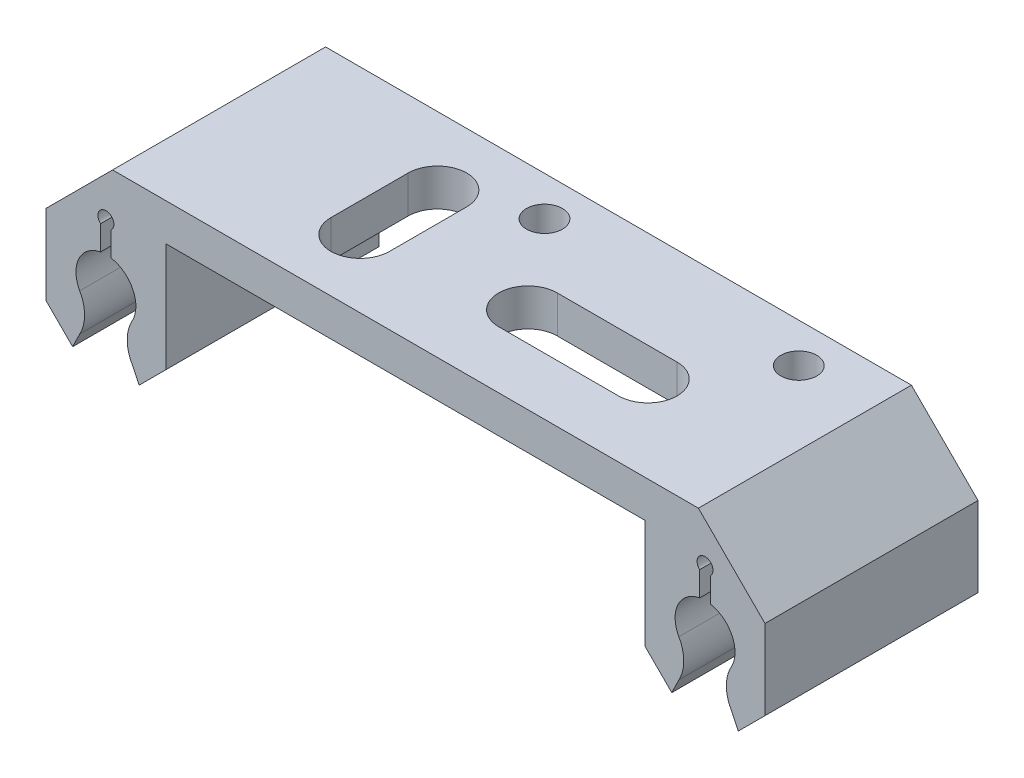
SolidWorks part; units mm, degrees
ref_plane "Front Plane" through (0, 0, 0) normal (0, 0, 1) x (1, 0, 0)
ref_plane "Top Plane" through (0, 0, 0) normal (0, 1, 0) x (1, 0, 0)
ref_plane "Right Plane" through (0, 0, 0) normal (1, 0, 0) x (0, 0, -1)
sketch "Sketch1" plane through (0, 0, 0) normal (0, 0, 1) x (1, 0, 0)
  line L0 (0, 0) -> (0, 13)
  line L1 (0, 13) -> (54, 13)
  line L2 (54, 13) -> (54, 0)
  line L3 (54, 0) -> (45, 0)
  line L4 (45, 0) -> (45, 10.2)
  line L5 (45, 10.2) -> (9, 10.2)
  line L6 (9, 10.2) -> (9, 0)
  line L7 (9, 0) -> (0, 0)
  point P4 (4.5, 0)
  dimension "D1" = 9
  dimension "D2" = 9
  dimension "D3" = 54
  dimension "D4" = 2.8
  dimension "D5" = 10.2
extrude "Boss-Extrude1" add sketch "Sketch1" along normal blind 16
chamfer "Chamfer1" distance 2 angle 45 4 edges at (54, 0, 8) (45, 0, 8) (0, 0, 8) (9, 0, 8)
sketch "Sketch2" plane through (0, 0, 16) normal (0, 0, 1) x (1, 0, 0)
  line L0 (2, 0) -> (7, 0) construction
  line L1 (47, 0) -> (52, 0) construction
  line L2 (9, 2) -> (9, 10.2) construction
  line L3 (45, 10.2) -> (45, 2) construction
  circle A0 centre (4.5, 5) radius 2.25
  circle A1 centre (49.5, 5) radius 2.25
  dimension "D5" = 4.5
  dimension "D6" = 4.5
  dimension "D1" = 5
  dimension "D2" = 5
  dimension "D3" = 4.5
  dimension "D4" = 4.5
extrude "Cut-Extrude1" cut sketch "Sketch2" against normal blind 16
sketch "Sketch3" plane through (0, 0, 16) normal (0, 0, 1) x (1, 0, 0)
  line L0 (2, 0) -> (7, 0) construction
  line L1 (4.1, 5) -> (4.1, 9.5) construction
  line L2 (4.1, 5) -> (4.9, 5) construction
  line L3 (4.1, 9.5) -> (4.9, 9.5) construction
  line L4 (4.9, 5) -> (4.9, 9.5) construction
  line L5 (4.1, 5) -> (4.9, 9.5) construction
  line L6 (4.1, 9.5) -> (4.9, 5) construction
  line L7 (2.5349, 3.9041) -> (6.4651, 3.9041)
  line L8 (2.5349, 1.0959) -> (2, 0)
  line L9 (2, 0) -> (7, 0)
  line L10 (7, 0) -> (6.4651, 1.0959)
  line L11 (2.9, 0) -> (2.9, 3.9041) construction
  line L12 (6.1, 3.9041) -> (6.1, 0) construction
  line L13 (4.1, 9.0528) -> (4.1, 6.7946)
  line L14 (4.1, 6.7946) -> (4.9, 6.7946)
  line L15 (4.9, 6.7946) -> (4.9, 9.0528)
  arc A0 (2.25, 0) -> (6.75, 0) centre (4.5, 0) cw construction
  circle A1 centre (4.5, 5) radius 2.25 construction
  arc A2 (2.5349, 3.9041) -> (2.5349, 1.0959) centre (0.0173, 2.5) cw
  arc A3 (6.4651, 3.9041) -> (6.4651, 1.0959) centre (8.9827, 2.5) ccw
  circle A4 centre (4.5, 9.5) radius 0.6 construction
  arc A5 (4.1, 9.0528) -> (4.9, 9.0528) centre (4.5, 9.5) cw
  point P6 (4.5, 7.25)
  dimension "D1" = 2.25
  dimension "D5" = 3.2
  dimension "D6" = 1.2
  dimension "D2" = 0.8
  dimension "D3" = 0.4
  dimension "D4" = 4.5
extrude "Cut-Extrude2" cut sketch "Sketch3" against normal blind 16
ref_plane "Plane1" through (27, 0, 0) normal (1, 0, 0) x (0, 0, -1)
mirror "Mirror1" about plane through (27, 0, 0) normal (1, 0, 0) of "Cut-Extrude2"
sketch "Sketch4" plane through (0, 13, 0) normal (0, 1, 0) x (1, 0, 0)
  line L0 (54, 0) -> (0, 0) construction
  line L1 (7.2, -16) -> (46.8, -16)
  line L2 (7.2, -16) -> (7.2, 0)
  line L3 (7.2, 0) -> (46.8, 0)
  line L4 (46.8, -16) -> (46.8, 0)
  line L5 (7.2, -16) -> (46.8, 0) construction
  line L6 (7.2, 0) -> (46.8, -16) construction
  line L7 (29.7, -9.5) -> (38.7, -9.5) construction
  line L8 (29.7, -7.3) -> (38.7, -7.3)
  line L9 (29.7, -11.7) -> (38.7, -11.7)
  line L10 (18.5, -5.1) -> (18.5, -10.9) construction
  line L11 (20.7, -5.1) -> (20.7, -10.9)
  line L12 (16.3, -5.1) -> (16.3, -10.9)
  circle A0 centre (43.5, -2.96) radius 1.6
  circle A1 centre (24.4, -2.96) radius 1.6
  arc A2 (29.7, -7.3) -> (29.7, -11.7) centre (29.7, -9.5) ccw
  arc A3 (38.7, -11.7) -> (38.7, -7.3) centre (38.7, -9.5) ccw
  arc A4 (20.7, -5.1) -> (16.3, -5.1) centre (18.5, -5.1) ccw
  arc A5 (16.3, -10.9) -> (20.7, -10.9) centre (18.5, -10.9) ccw
  point P0 (27, -8)
  point P8 (27, 0)
  point P12 (34.2, -9.5)
  point P21 (18.5, -8)
  point P26 (0, 0)
  point P27 (7.2, -8)
  dimension "D4" = 3.2
  dimension "D5" = 3.2
  dimension "D1" = 8
  dimension "D2" = 39.6
  dimension "D3" = 16
  dimension "D6" = 3.3
  dimension "D7" = 2.96
  dimension "D8" = 22.4
  dimension "D9" = 4.4
  dimension "D10" = 6.5
  dimension "D11" = 9
  dimension "D12" = 12.6
  dimension "D13" = 4.4
  dimension "D14" = 11.3
  dimension "D15" = 5.8
sketch "Sketch5" plane through (0, 13, 0) normal (0, 1, 0) x (1, 0, 0)
  line L0 (18.5, -5.1) -> (18.5, -10.9) construction
  line L1 (20.7, -5.1) -> (20.7, -10.9)
  line L2 (16.3, -5.1) -> (16.3, -10.9)
  line L3 (29.7, -9.5) -> (38.7, -9.5) construction
  line L4 (29.7, -7.3) -> (38.7, -7.3)
  line L5 (29.7, -11.7) -> (38.7, -11.7)
  arc A0 (20.7, -5.1) -> (16.3, -5.1) centre (18.5, -5.1) ccw
  arc A1 (16.3, -10.9) -> (20.7, -10.9) centre (18.5, -10.9) ccw
  arc A2 (29.7, -7.3) -> (29.7, -11.7) centre (29.7, -9.5) ccw
  arc A3 (38.7, -11.7) -> (38.7, -7.3) centre (38.7, -9.5) ccw
  circle A4 centre (24.4, -2.96) radius 1.35
  circle A5 centre (43.5, -2.96) radius 1.35
  point P4 (18.5, -8)
  point P9 (34.2, -9.5)
  point P24 (34.2, -11.7)
  dimension "D3" = 2.7
  dimension "D4" = 2.7
  dimension "D1" = 4.4
  dimension "D2" = 4.4
extrude "Cut-Extrude3" cut sketch "Sketch5" against normal blind 16
chamfer "Chamfer3" distance 5 angle 45 2 edges at (54, 13, 8) (0, 13, 8)
